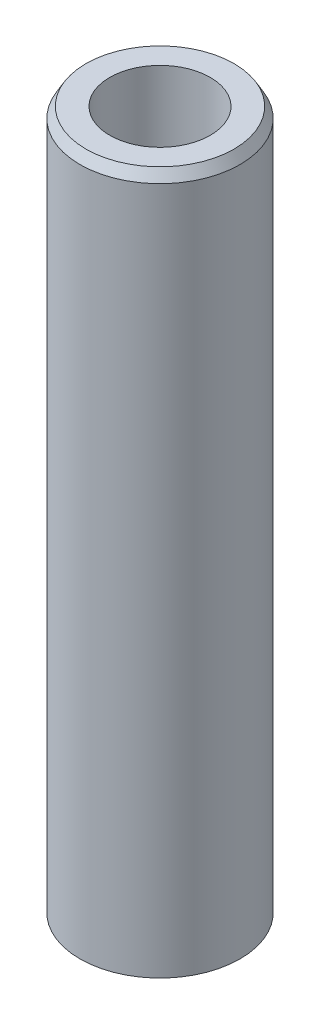
SolidWorks part; units mm, degrees
ref_plane "Front Plane" through (0, 0, 0) normal (0, 0, 1) x (1, 0, 0)
ref_plane "Top Plane" through (0, 0, 0) normal (0, 1, 0) x (1, 0, 0)
ref_plane "Right Plane" through (0, 0, 0) normal (1, 0, 0) x (0, 0, -1)
sketch "Sketch1" plane through (0, 0, 0) normal (0, 1, 0) x (1, 0, 0)
  circle A0 centre (0, 0) radius 7.5
  dimension "SHAFT_OD" = 15
extrude "Boss-Extrude1" add sketch "Sketch1" along normal blind 65.9909
sketch "Sketch2" plane through (0, 0, 0) normal (0, 1, 0) x (1, 0, 0)
  circle A0 centre (0, 0) radius 4.7059
  dimension "BORE_D" = 9.4119
extrude "Cut-Extrude1" cut sketch "Sketch2" along normal through all
chamfer "Chamfer1" distance 0.974 angle 30 2 edges at (0, 65.9909, 7.5) (0, 0, 7.5) first distance on face at (0, 65.9909, 7.5) first distance on face at (0, 0, 4.7059)
